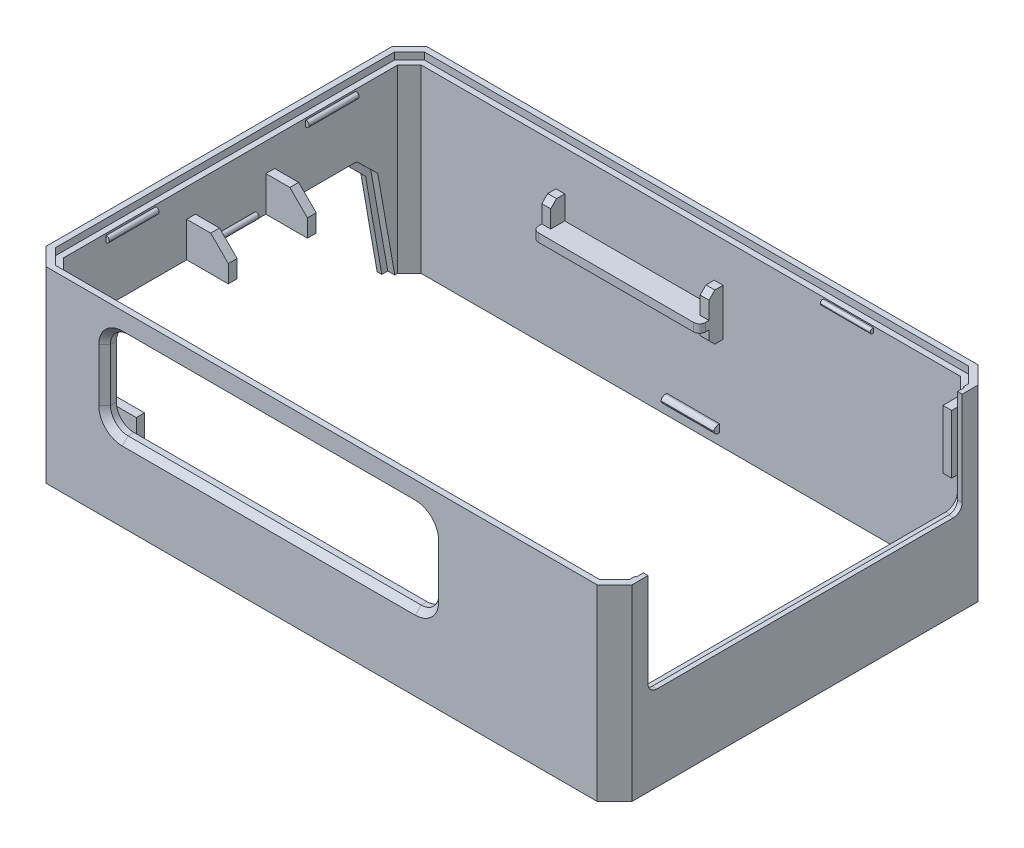
SolidWorks part; units mm, degrees
ref_plane "前视基准面" through (0, 0, 0) normal (0, 0, 1) x (1, 0, 0)
ref_plane "上视基准面" through (0, 0, 0) normal (0, 1, 0) x (1, 0, 0)
ref_plane "右视基准面" through (0, 0, 0) normal (1, 0, 0) x (0, 0, -1)
sketch "草图1" plane through (0, 0, 0) normal (0, 1, 0) x (1, 0, 0)
  line L1 (-50, 32.5) -> (50, 32.5)
  line L2 (-50, 32.5) -> (-50, -32.5)
  line L3 (-50, -32.5) -> (50, -32.5)
  line L4 (50, 32.5) -> (50, -32.5)
  line L5 (-50, 32.5) -> (50, -32.5) construction
  line L6 (-50, -32.5) -> (50, 32.5) construction
  point P0 (0, 0)
  dimension "D1" = 65
  dimension "D2" = 100
extrude "凸台-拉伸1" add sketch "草图1" along normal blind 32
sketch "草图2" plane through (0, 32, 0) normal (0, 1, 0) x (1, 0, 0)
  line L8 (48, -30.5) -> (48, 30.5)
  line L9 (48, 30.5) -> (-48, 30.5)
  line L10 (-48, 30.5) -> (-48, -30.5)
  line L11 (-48, -30.5) -> (48, -30.5)
  line L12 (48, -30.5) -> (48, 30.5)
  line L13 (48, 30.5) -> (-48, 30.5)
  line L14 (-48, 30.5) -> (-48, -30.5)
  line L15 (-48, -30.5) -> (48, -30.5)
  dimension "D1" = 2
extrude "切除-拉伸1" cut sketch "草图2" against normal through all
sketch "草图4" plane through (-50, 0, 0) normal (-1, 0, 0) x (0, 0, 1)
  line L0 (-32.5, 0) -> (32.5, 0) construction
  line L3 (-28, 0) -> (28, 0)
  line L7 (-25.0863, 16.5) -> (-21.5, 20)
  line L8 (21.5, 20) -> (25.09, 16.5)
  line L9 (32.5, 32) -> (32.5, 0) construction
  line L12 (-25.0863, 16.5) -> (-28, 0)
  line L13 (-21.5, 20) -> (21.5, 20)
  line L14 (25.09, 16.5) -> (28, 0)
  line L15 (-32.5, 0) -> (32.5, 0) construction
  line L16 (-32.5, 32) -> (-32.5, 0) construction
  dimension "D1" = 16.5
  dimension "D2" = 20
  dimension "D3" = 4.5
  dimension "D4" = 4.5
  dimension "D5" = 11
  dimension "D6" = 11
  dimension "D7" = 7.4137
  dimension "D8" = 7.41
extrude "切除-拉伸2" cut sketch "草图4" against normal blind 2
sketch "草图7" plane through (0, 0, 32.5) normal (0, 0, 1) x (1, 0, 0)
  line L16 (-37, 28) -> (-37, 13)
  line L17 (19, 28) -> (-37, 28)
  line L18 (19, 13) -> (19, 28)
  line L19 (-37, 13) -> (19, 13)
extrude "切除-拉伸3" cut sketch "草图7" against normal blind 2.5
fillet "圆角7" radius 3 4 edges at (-37, 28, 31.5) (19, 28, 31.5) (19, 13, 31.5) (-37, 13, 31.5)
chamfer "倒角1" distance 1 angle 45 8 edges at (-9, 28, 32.5) (-36.1213, 27.1213, 32.5) (18.1213, 27.1213, 32.5) (-37, 20.5, 32.5) (19, 20.5, 32.5) (-36.1213, 13.8787, 32.5) (18.1213, 13.8787, 32.5) (-9, 13, 32.5)
sketch "草图9" plane through (50, 0, 0) normal (1, 0, 0) x (0, 0, -1)
  line L0 (-25.6851, 37.094) -> (-12.3808, 37.094)
  line L1 (-25.6851, 37.094) -> (-25.6851, 22.8739)
  line L2 (-25.6851, 22.8739) -> (-12.3808, 22.8739)
  line L3 (-12.3808, 37.094) -> (-12.3808, 22.8739)
  line L4 (-7.5808, 37.094) -> (5.5192, 37.094)
  line L5 (-7.5808, 37.094) -> (-7.5808, 22.8739)
  line L6 (-7.5808, 22.8739) -> (5.5192, 22.8739)
  line L7 (5.5192, 37.094) -> (5.5192, 22.8739)
  line L8 (10, 33.8806) -> (25.4692, 33.8806)
  line L9 (10, 33.8806) -> (10, 21.8806)
  line L10 (10, 21.8806) -> (25.4692, 21.8806)
  line L11 (25.4692, 33.8806) -> (25.4692, 21.8806)
  line L14 (-32.5, 32) -> (-32.5, 0) construction
  line L15 (32.5, 32) -> (32.5, 0) construction
  dimension "D1" = 14.2201
  dimension "D2" = 13.1
  dimension "D3" = 6.8149
  dimension "D4" = 24.9192
  dimension "D5" = 7.0308
  dimension "D6" = 12
ref_plane "基准面4" through (0, 19.25, 0) normal (0, -1, 0) x (-1, 0, 0)
sketch "草图10" plane through (0, 19.25, 0) normal (0, -1, 0) x (-1, 0, 0)
  line L0 (-41.8403, 31.4577) -> (-41.8403, -31.3544)
sketch "草图11" plane through (48, 0, 0) normal (-1, 0, 0) x (0, 0, 1)
  line L1 (-8.8, 24.925) -> (-7.3, 24.925)
  line L2 (-8.8, 24.925) -> (-8.8, 19.925)
  line L3 (-8.8, 19.925) -> (-7.3, 19.925)
  line L4 (-7.3, 24.925) -> (-7.3, 19.925)
  line L5 (32.5, 32) -> (25.6851, 32) construction
  line L6 (9, 24.925) -> (10.5, 24.925)
  line L7 (9, 24.925) -> (9, 19.925)
  line L8 (9, 19.925) -> (10.5, 19.925)
  line L9 (10.5, 24.925) -> (10.5, 19.925)
  line L11 (32.5, 32) -> (32.5, 0) construction
  line L12 (-32.5, 32) -> (-32.5, 0) construction
  dimension "D1" = 1.5
  dimension "D2" = 1.5
  dimension "D3" = 22
  dimension "D4" = 23.7
  dimension "D5" = 5
  dimension "D6" = 12.075
sketch "草图17" plane through (-48, 0, 0) normal (1, 0, 0) x (0, 0, -1)
  line L1 (-6, 20) -> (-7.5, 20)
  line L2 (-6, 20) -> (-6, 26)
  line L3 (-6, 26) -> (-7.5, 26)
  line L4 (-7.5, 20) -> (-7.5, 26)
  line L5 (32.5, 32) -> (32.5, 0) construction
  line L6 (6, 20) -> (7.5, 20)
  line L7 (6, 20) -> (6, 26)
  line L8 (6, 26) -> (7.5, 26)
  line L9 (7.5, 20) -> (7.5, 26)
  line L10 (-21.5, 20) -> (21.5, 20) construction
  line L12 (-32.5, 32) -> (-32.5, 0) construction
  dimension "D1" = 1.5
  dimension "D2" = 1.5
  dimension "D3" = 25
  dimension "D4" = 25
  dimension "D5" = 6
extrude "凸台-拉伸6" add sketch "草图17" along normal blind 7.1
chamfer "倒角6" distance 3 angle 45 2 edges at (-40.9, 26, -6.75) (-40.9, 26, 6.75)
sketch "草图24" plane through (48, 0, 0) normal (-1, 0, 0) x (0, 0, 1)
  line L1 (-4.5, 3.3) -> (4.5, 3.3)
  line L2 (-4.5, 3.3) -> (-4.5, 1.8)
  line L3 (-4.5, 1.8) -> (4.5, 1.8)
  line L4 (4.5, 3.3) -> (4.5, 1.8)
  line L5 (-4.5, 3.3) -> (4.5, 1.8) construction
  line L6 (-4.5, 1.8) -> (4.5, 3.3) construction
  line L7 (30.5, 0) -> (-30.5, 0) construction
  line L8 (32.5, 0) -> (-32.5, 0) construction
  point P0 (0, 2.55)
  point P10 (0, 0)
  dimension "D1" = 1.5
  dimension "D2" = 1.8
  dimension "D3" = 9
extrude "凸台-拉伸10" add sketch "草图24" along normal blind 1
fillet "圆角15" radius 0.8 2 edges at (47, 3.3, 0) (47, 1.8, 0)
sketch "草图25" plane through (0, 0, 30.5) normal (0, 0, -1) x (-1, 0, 0)
  line L0 (48, 0) -> (-48, 0) construction
  line L1 (-4.9102, 3.2365) -> (4.0898, 3.2365)
  line L2 (-4.9102, 3.2365) -> (-4.9102, 1.9365)
  line L3 (-4.9102, 1.9365) -> (4.0898, 1.9365)
  line L4 (4.0898, 3.2365) -> (4.0898, 1.9365)
  line L5 (-4.9102, 3.2365) -> (4.0898, 1.9365) construction
  line L6 (-4.9102, 1.9365) -> (4.0898, 3.2365) construction
  line L8 (50, 32) -> (50, 0) construction
  point P0 (-0.4102, 2.5865)
  dimension "D1" = 9
  dimension "D2" = 1.3
  dimension "D3" = 2.5865
  dimension "D4" = 50.4102
extrude "凸台-拉伸11" add sketch "草图25" along normal blind 1
sketch "草图26" plane through (0, 0, -30.5) normal (0, 0, 1) x (1, 0, 0)
  line L4 (-4.0898, 3.2365) -> (-4.0898, 1.9365)
  line L5 (4.9102, 3.2365) -> (-4.0898, 3.2365)
  line L6 (4.9102, 1.9365) -> (4.9102, 3.2365)
  line L7 (-4.0898, 1.9365) -> (4.9102, 1.9365)
  line L8 (-4.0898, 3.2365) -> (-4.0898, 1.9365)
  line L9 (4.9102, 3.2365) -> (-4.0898, 3.2365)
  line L10 (4.9102, 1.9365) -> (4.9102, 3.2365)
  line L11 (-4.0898, 1.9365) -> (4.9102, 1.9365)
  dimension "D1" = 0
extrude "凸台-拉伸12" add sketch "草图26" along normal blind 1
fillet "圆角16" radius 0.8 4 edges at (0.4102, 1.9365, -29.5) (0.4102, 3.2365, -29.5) (0.4102, 1.9365, 29.5) (0.4102, 3.2365, 29.5)
chamfer "倒角7" distance 2 angle 45 4 edges at (-48, 16, -30.5) (-48, 16, 30.5) (48, 16, -30.5) (48, 16, 30.5)
chamfer "倒角8" distance 3 angle 45 4 edges at (-50, 16, 32.5) (-50, 16, -32.5) (50, 16, -32.5) (50, 16, 32.5)
sketch "草图28" plane through (-50, 0, 0) normal (-1, 0, 0) x (0, 0, 1)
  line L27 (-29.3, 22.3393) -> (-29.3, 0)
  line L28 (-29.3, 0) -> (-26.9872, 0)
  line L29 (-26.9872, 0) -> (-24.2154, 15.8784)
  line L30 (-24.2154, 15.8784) -> (-21.1176, 18.9896)
  line L31 (-21.1176, 18.9896) -> (21.1176, 18.9896)
  line L32 (21.1176, 18.9896) -> (24.2152, 15.8784)
  line L33 (24.2152, 15.8784) -> (27.008, 0)
  line L34 (27.008, 0) -> (29.3, 0)
  line L35 (29.3, 0) -> (29.3, 22.3393)
  line L36 (29.3, 22.3393) -> (-29.3, 22.3393)
  line L37 (28.5, 0) -> (-28.5, 0) construction
  line L38 (-29.5, 0) -> (-28, 0) construction
  line L39 (28, 0) -> (29.5, 0) construction
extrude "凸台-拉伸13" add sketch "草图28" against normal blind 0.8
sketch "草图30" plane through (-50, 0, 0) normal (-1, 0, 0) x (0, 0, 1)
  line L20 (27.008, 0) -> (29.5, 0) construction
  line L21 (-29.5, 0) -> (-26.9872, 0) construction
  line L22 (-29.5, 32) -> (-29.5, 0) construction
  line L23 (29.5, 0) -> (29.5, 32) construction
  line L24 (-29.5, 32) -> (29.5, 32) construction
  line L32 (27.58, 0) -> (24.7738, 16.1781)
  line L33 (24.7738, 16.1781) -> (21.3669, 19.6)
  line L34 (21.3669, 19.6) -> (-21.3669, 19.6)
  line L35 (-21.3669, 19.6) -> (-24.7741, 16.1781)
  line L36 (-24.7741, 16.1781) -> (-27.5845, 0)
  dimension "D1" = 1.9155
  dimension "D2" = 1.92
  dimension "D3" = 4.7262
  dimension "D4" = 8.1331
  dimension "D5" = 4.7259
  dimension "D6" = 8.1331
  dimension "D7" = 12.4
  dimension "D8" = 15.8219
sketch "草图35" plane through (48, 0, 0) normal (-1, 0, 0) x (0, 0, 1)
  line L0 (-28, 32) -> (28, 32)
  line L1 (-28, 32) -> (-28, 14)
  line L2 (-28, 14) -> (28, 14)
  line L3 (28, 32) -> (28, 14)
  line L4 (32.5, 0) -> (32.5, 32) construction
  line L5 (-32.5, 32) -> (-32.5, 0) construction
  line L6 (28.5, 32) -> (-28.5, 32) construction
  dimension "D1" = 18
  dimension "D3" = 4.5
  dimension "D4" = 4.5
extrude "切除-拉伸6" cut sketch "草图35" against normal blind 1.2
fillet "圆角17" radius 2 2 edges at (48.6, 14, -28) (48.6, 14, 28)
sketch "草图39" plane through (49.2, 0, 0) normal (-1, 0, 0) x (0, 0, 1)
  line L0 (32.5, 0) -> (32.5, 32) construction
  line L1 (-32.5, 32) -> (-32.5, 0) construction
  line L2 (28, 32) -> (-28, 32) construction
  line L3 (29.5, 32) -> (-29.5, 32) construction
  line L4 (29.5, 0) -> (-29.5, 0) construction
  line L12 (-26.8, 32) -> (-26.8, 16)
  line L13 (-25.3, 14.5) -> (25.3, 14.5)
  line L14 (26.8, 16) -> (26.8, 32)
  line L15 (26.8, 32) -> (-26.8, 32)
  arc A6 (-26.8, 16) -> (-25.3, 14.5) centre (-25.3, 16) ccw
  arc A7 (25.3, 14.5) -> (26.8, 16) centre (25.3, 16) ccw
  point P0 (0, 0)
  dimension "D1" = 7.2
  dimension "D2" = 7.2
  dimension "D3" = 16
  dimension "D4" = 14.5
extrude "切除-拉伸7" cut sketch "草图39" against normal blind 1.2
ref_plane "基准面5" through (-50, 32, 29.5) normal (0.7071, 0, 0.7071) x (0.7071, 0, -0.7071)
sketch "草图42" plane through (-48, 0, 0) normal (1, 0, 0) x (0, 0, -1)
  line L0 (32.5, 0) -> (32.5, 32) construction
  line L1 (12.8, 30.5) -> (21.3, 30.5)
  line L2 (12.8, 30.5) -> (12.8, 29.5)
  line L3 (12.8, 29.5) -> (21.3, 29.5)
  line L4 (21.3, 30.5) -> (21.3, 29.5)
  line L5 (12.8, 30.5) -> (21.3, 29.5) construction
  line L6 (12.8, 29.5) -> (21.3, 30.5) construction
  line L7 (-4.2291, 21.2667) -> (4.2291, 21.2667)
  line L8 (-4.2291, 21.2667) -> (-4.2291, 20.2667)
  line L9 (-4.2291, 20.2667) -> (4.2291, 20.2667)
  line L10 (4.2291, 21.2667) -> (4.2291, 20.2667)
  line L11 (-4.2291, 21.2667) -> (4.2291, 20.2667) construction
  line L12 (-4.2291, 20.2667) -> (4.2291, 21.2667) construction
  line L13 (-32.5, 32) -> (-32.5, 0) construction
  line L14 (28.5, 32) -> (-28.5, 32) construction
  line L15 (-12.8, 29.5) -> (-21.3, 29.5)
  line L16 (-12.8, 29.5) -> (-12.8, 30.5)
  line L17 (-12.8, 30.5) -> (-21.3, 30.5)
  line L18 (-21.3, 29.5) -> (-21.3, 30.5)
  line L19 (-12.8, 29.5) -> (-21.3, 30.5) construction
  line L20 (-12.8, 30.5) -> (-21.3, 29.5) construction
  point P0 (17.05, 30)
  point P5 (0, 20.7667)
  point P16 (-17.05, 30)
  dimension "D1" = 1
  dimension "D2" = 1
  dimension "D3" = 2
  dimension "D4" = 11.2
  dimension "D5" = 8.5
  dimension "D6" = 1
  dimension "D7" = 8.5
  dimension "D8" = 11.2
  dimension "D9" = 2
extrude "凸台-拉伸14" add sketch "草图42" along normal blind 0.6
fillet "圆角18" radius 0.5 6 edges at (-47.4, 20.2667, 0) (-47.4, 21.2667, 0) (-47.4, 29.5, -17.05) (-47.4, 30.5, -17.05) (-47.4, 30.5, 17.05) (-47.4, 29.5, 17.05)
sketch "草图44" plane through (0, 0, -28) normal (0, 0, 1) x (1, 0, 0)
  line L0 (48, 32) -> (48, 16) construction
  line L1 (48, 28.5) -> (46.5, 28.5)
  line L2 (48, 28.5) -> (48, 18.5)
  line L3 (48, 18.5) -> (46.5, 18.5)
  line L4 (46.5, 28.5) -> (46.5, 18.5)
  line L5 (50, 14.5) -> (49.2, 14.5) construction
  dimension "D1" = 1.5
  dimension "D2" = 10
  dimension "D3" = 4
extrude "凸台-拉伸15" add sketch "草图44" along normal blind 1 and the other way up to surface (2.5 mm away) other way up to face at (0, 16, -30.5)
sketch "草图45" plane through (0, 0, 28) normal (0, 0, -1) x (-1, 0, 0)
  line L4 (-48, 28.5) -> (-48, 18.5)
  line L5 (-46.5, 28.5) -> (-48, 28.5)
  line L6 (-46.5, 18.5) -> (-46.5, 28.5)
  line L7 (-48, 18.5) -> (-46.5, 18.5)
  line L8 (-48, 28.5) -> (-48, 18.5)
  line L9 (-46.5, 28.5) -> (-48, 28.5)
  line L10 (-46.5, 18.5) -> (-46.5, 28.5)
  line L11 (-48, 18.5) -> (-46.5, 18.5)
  dimension "D1" = 0
extrude "凸台-拉伸16" add sketch "草图45" along normal blind 1 and the other way up to surface (2.5 mm away) other way up to face at (0, 16, 30.5)
ref_plane "基准面6" through (48, 0, -28.5) normal (0, 0, -1) x (-1, 0, 0)
sketch "草图48" plane through (0, 32, 0) normal (0, 1, 0) x (1, 0, 0)
  line L0 (48, 28.5) -> (46, 30.5)
  line L1 (46, 30.5) -> (-46, 30.5)
  line L2 (48, 28.5) -> (48, -28.5)
  line L3 (46, -30.5) -> (-46, -30.5)
  line L4 (-48, 28.5) -> (-48, -28.5)
  line L5 (48, -28.5) -> (46, -30.5)
  line L6 (-46, -30.5) -> (-48, -28.5)
  line L7 (-46, 30.5) -> (-48, 28.5)
  line L8 (49, 28.9142) -> (49, -28.9142)
  line L9 (49, -28.9142) -> (46.4142, -31.5)
  line L10 (46.4142, -31.5) -> (-46.4142, -31.5)
  line L11 (-46.4142, -31.5) -> (-49, -28.9142)
  line L12 (-49, 28.9142) -> (-49, -28.9142)
  line L13 (-46.4142, 31.5) -> (-49, 28.9142)
  line L14 (46.4142, 31.5) -> (-46.4142, 31.5)
  line L15 (49, 28.9142) -> (46.4142, 31.5)
  point P0 (48, 30.5)
  point P1 (-48, -30.5)
  point P2 (48, -30.5)
  point P3 (-48, 30.5)
  dimension "D2" = 1
extrude "切除-拉伸8" cut sketch "草图48" against normal blind 1.2
sketch "草图49" plane through (0, 0, -30.5) normal (0, 0, 1) x (1, 0, 0)
  line L0 (50, 32) -> (50, 16) construction
  line L1 (22.6985, 30.6) -> (31.1985, 30.6)
  line L2 (22.6985, 30.6) -> (22.6985, 29.8)
  line L3 (22.6985, 29.8) -> (31.1985, 29.8)
  line L4 (31.1985, 30.6) -> (31.1985, 29.8)
  line L5 (22.6985, 30.6) -> (31.1985, 29.8) construction
  line L6 (22.6985, 29.8) -> (31.1985, 30.6) construction
  line L8 (46.4142, 32) -> (-46.4142, 32) construction
  point P0 (26.9485, 30.2)
  point P7 (0, 0)
  point P10 (0, 0)
  dimension "D1" = 0.8
  dimension "D2" = 8.5
  dimension "D3" = 18.8015
  dimension "D4" = 1.8
extrude "凸台-拉伸17" add sketch "草图49" along normal blind 0.6
sketch "草图50" plane through (0, 0, 30.5) normal (0, 0, -1) x (-1, 0, 0)
  line L4 (-31.1985, 30.6) -> (-31.1985, 29.8)
  line L5 (-22.6985, 30.6) -> (-31.1985, 30.6)
  line L6 (-22.6985, 29.8) -> (-22.6985, 30.6)
  line L7 (-31.1985, 29.8) -> (-22.6985, 29.8)
  line L8 (-31.1985, 30.6) -> (-31.1985, 29.8)
  line L9 (-22.6985, 30.6) -> (-31.1985, 30.6)
  line L10 (-22.6985, 29.8) -> (-22.6985, 30.6)
  line L11 (-31.1985, 29.8) -> (-22.6985, 29.8)
  dimension "D1" = 0
extrude "凸台-拉伸18" add sketch "草图50" along normal blind 0.6
fillet "圆角20" radius 0.4 4 edges at (26.9485, 30.6, 29.9) (26.9485, 29.8, 29.9) (26.9485, 30.6, -29.9) (26.9485, 29.8, -29.9)
sketch "草图51" plane through (0, 0, 30.5) normal (0, 0, -1) x (-1, 0, 0)
  line L0 (35.1966, 7.8) -> (35.1966, 9.1168)
  line L1 (-21, 13.8) -> (-22.5, 13.8)
  line L3 (-17, 7.8) -> (-22.5, 7.8)
  line L4 (-22.5, 13.8) -> (-22.5, 7.8)
  line L5 (46, 0) -> (-46, 0) construction
  line L6 (-17, 7.8) -> (-17, 9.1168)
  line L7 (-17, 9.1168) -> (-21, 9.1168)
  line L8 (-21, 9.1168) -> (-21, 13.8)
  line L9 (35.1966, 9.1168) -> (39.1966, 9.1168)
  line L10 (40.6966, 13.8) -> (39.1966, 13.8)
  line L11 (40.6966, 13.8) -> (40.6966, 7.8)
  line L12 (40.6966, 7.8) -> (35.1966, 7.8)
  line L13 (39.1966, 9.1168) -> (39.1966, 13.8)
  line L14 (50, 0) -> (50, 32) construction
  line L15 (-50, 32) -> (-50, 0) construction
  dimension "D1" = 1.5
  dimension "D2" = 6
  dimension "D3" = 1.5
  dimension "D4" = 7.8
  dimension "D5" = 6
  dimension "D6" = 5.5
  dimension "D7" = 9.3034
  dimension "D8" = 27.5
  dimension "D9" = 5.5
extrude "凸台-拉伸19" add sketch "草图51" along normal blind 3
sketch "草图52" plane through (21, 0, 0) normal (-1, 0, 0) x (0, 0, 1)
  line L0 (27.5, 9.1168) -> (27.5, 13.8) construction
  line L1 (27.5, 13.8) -> (28.9, 13.8)
  line L2 (27.5, 13.8) -> (27.5, 9.1168)
  line L3 (27.5, 9.1168) -> (28.9, 9.1168)
  line L4 (28.9, 13.8) -> (28.9, 9.1168)
  line L5 (27.5, 13.8) -> (30.5, 13.8) construction
  line L6 (27.5, 9.1168) -> (30.5, 9.1168) construction
  dimension "D1" = 1.4
extrude "凸台-拉伸20" add sketch "草图52" along normal blind 4
sketch "草图53" plane through (-39.1966, 0, 0) normal (1, 0, 0) x (0, 0, -1)
  line L4 (-27.5, 7.8) -> (-27.5, 13.8)
  line L5 (-28.9, 9.1168) -> (-30.5, 9.1168)
  line L6 (-28.9, 13.8) -> (-28.9, 9.1168)
  line L7 (-27.5, 13.8) -> (-28.9, 13.8)
  line L8 (-27.5, 7.8) -> (-27.5, 13.8)
  line L9 (-28.9, 9.1168) -> (-30.5, 9.1168)
  line L10 (-28.9, 13.8) -> (-28.9, 9.1168)
  line L11 (-27.5, 13.8) -> (-28.9, 13.8)
  line L14 (-30.5, 9.1168) -> (-30.5, 7.8)
  line L15 (-30.5, 9.1168) -> (-30.5, 7.8)
  line L16 (-30.5, 7.8) -> (-27.5, 7.8)
  line L17 (-30.5, 7.8) -> (-27.5, 7.8)
  dimension "D1" = 0
extrude "凸台-拉伸21" add sketch "草图53" along normal blind 4
sketch "草图55" plane through (0, 0, -30.5) normal (0, 0, 1) x (1, 0, 0)
  line L0 (-50, 0) -> (-50, 32) construction
  line L1 (-23, 20) -> (5.5, 20)
  line L2 (-23, 20) -> (-23, 18.6)
  line L3 (-23, 18.6) -> (5.5, 18.6)
  line L4 (5.5, 20) -> (5.5, 18.6)
  line L5 (-47, 32) -> (47, 32) construction
  dimension "D1" = 1.4
  dimension "D2" = 27
  dimension "D3" = 12
  dimension "D4" = 28.5
extrude "凸台-拉伸22" add sketch "草图55" along normal blind 4
sketch "草图56" plane through (0, 0, -30.5) normal (0, 0, 1) x (1, 0, 0)
  line L0 (-50, 0) -> (-50, 32) construction
  line L1 (-23, 24) -> (-21.5, 24)
  line L2 (-23, 24) -> (-23, 16)
  line L3 (-23, 16) -> (-21.5, 16)
  line L4 (-21.5, 24) -> (-21.5, 16)
  line L5 (4, 24) -> (5.5, 24)
  line L6 (4, 24) -> (4, 16)
  line L7 (4, 16) -> (5.5, 16)
  line L8 (5.5, 24) -> (5.5, 16)
  line L9 (-47, 32) -> (47, 32) construction
  dimension "D1" = 1.5
  dimension "D2" = 8
  dimension "D3" = 27
  dimension "D4" = 54
  dimension "D5" = 8
extrude "凸台-拉伸23" add sketch "草图56" along normal blind 2.4
chamfer "倒角9" distance 1 angle 45 4 edges at (-22.25, 16, -28.1) (4.75, 16, -28.1) (4.75, 24, -28.1) (-22.25, 24, -28.1)
fillet "圆角21" radius 1 2 edges at (5.5, 19.3, -26.5) (-23, 19.3, -26.5)
